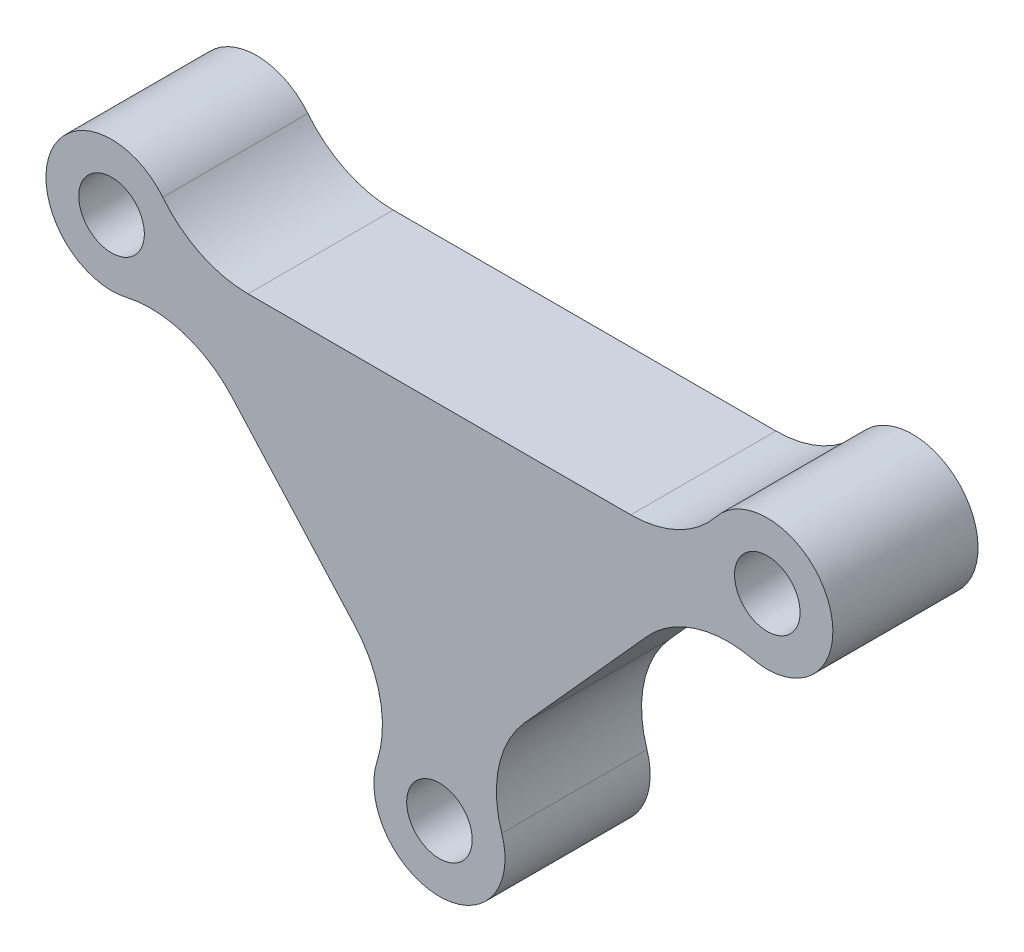
SolidWorks part; units mm, degrees
ref_plane "Plan de face" through (0, 0, 0) normal (0, 0, 1) x (1, 0, 0)
ref_plane "Plan de dessus" through (0, 0, 0) normal (0, 1, 0) x (1, 0, 0)
ref_plane "Plan de droite" through (0, 0, 0) normal (1, 0, 0) x (0, 0, -1)
sketch "Esquisse2" plane through (0, 0, 0) normal (0, 0, 1) x (1, 0, 0)
  line L0 (-13.5, 10) -> (13.5, 10)
  line L1 (13.5, 10) -> (0, -5)
  line L2 (0, -5) -> (-13.5, 10)
  line L3 (0, 0) -> (-13.5, 10) construction
  line L4 (0, 0) -> (13.5, 10) construction
  circle A0 centre (-15, 10) radius 3
  circle A1 centre (-15, 10) radius 1.5
  circle A2 centre (15, 10) radius 3
  circle A3 centre (15, 10) radius 1.5
  circle A4 centre (0, -6.5) radius 3
  circle A5 centre (0, -6.5) radius 1.5
  dimension "D2" = 3
  dimension "D3" = 6
  dimension "D1" = 5
  dimension "D4" = 10
  dimension "D5" = 15
extrude "Boss.-Extru.1" add sketch "Esquisse2" along normal blind 6.64 contours A4 L1 A2 L0 A0 L2 | L1 A5 L2 A4 | L1 A4 L2 | A3 | A1 | L0 L1 L2 | A2 | A0 | A4 | A5 region at (-15, 10, 0) region at (0, 5.0337, 0) region at (15, 10, 0) region at (0, -4.0518, 0) region at (-0.6346, -4.4193, 0)
fillet "Congé1" radius 5 6 edges at (-12, 10, 3.32) (-12.3081, 8.6757, 3.32) (-1.1454, -3.7273, 3.32) (12.3081, 8.6757, 3.32) (12, 10, 3.32) (1.1454, -3.7273, 3.32)
